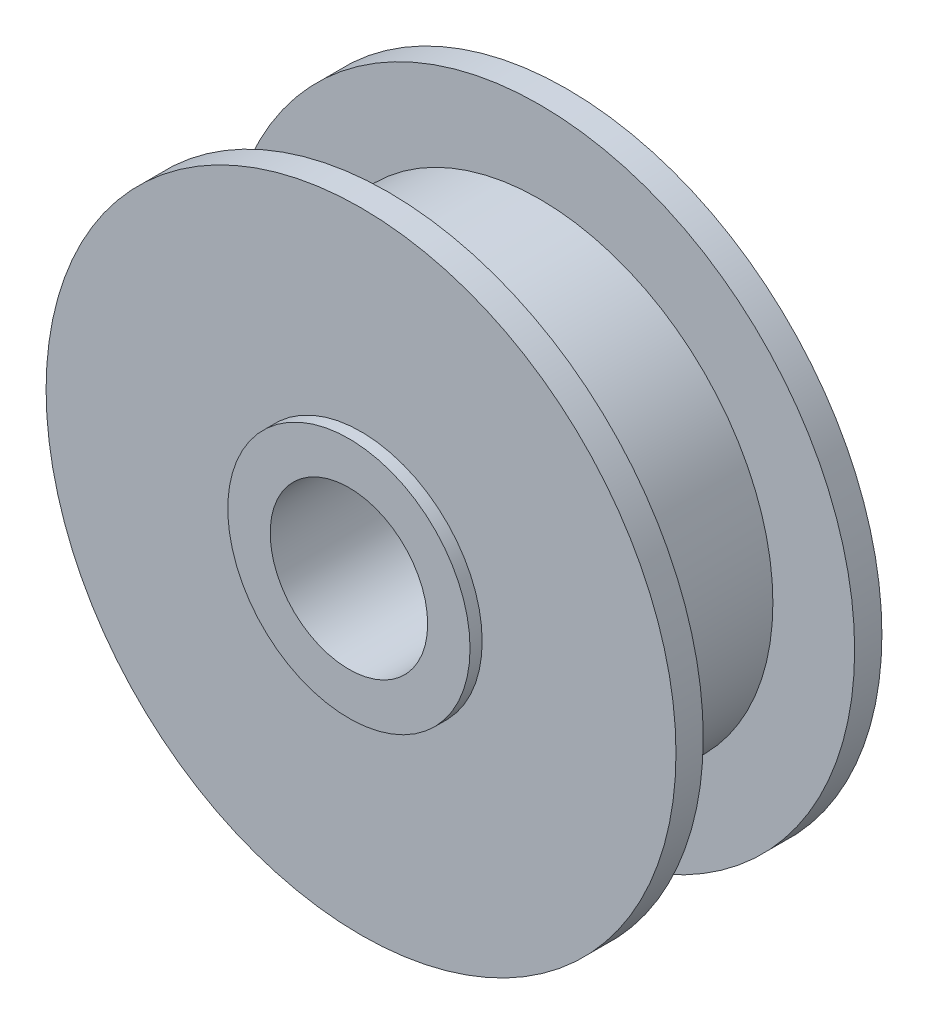
SolidWorks part; units mm, degrees
ref_plane "Front Plane" through (0, 0, 0) normal (0, 0, 1) x (1, 0, 0)
ref_plane "Top Plane" through (0, 0, 0) normal (0, 1, 0) x (1, 0, 0)
ref_plane "Right Plane" through (0, 0, 0) normal (1, 0, 0) x (0, 0, -1)
sketch "Sketch1" plane through (0, 0, 0) normal (1, 0, 0) x (0, 0, -1)
  line L0 (0, 1.3) -> (0, 2)
  line L1 (0, 2) -> (0.2, 2)
  line L2 (0.2, 2) -> (0.2, 5.2)
  line L3 (0.2, 5.2) -> (0.65, 5.2)
  line L4 (0.65, 5.2) -> (0.65, 3.85)
  line L5 (0.65, 3.85) -> (3.15, 3.85)
  line L6 (3.15, 3.85) -> (3.15, 5.2)
  line L7 (3.15, 5.2) -> (3.6, 5.2)
  line L8 (3.6, 5.2) -> (3.6, 2)
  line L9 (3.6, 2) -> (3.8, 2)
  line L10 (3.8, 2) -> (3.8, 1.3)
  line L11 (3.8, 1.3) -> (0, 1.3)
  line L12 (0, 0) -> (3.8, 0) construction
  dimension "D1" = 5.2
  dimension "D2" = 2
  dimension "D3" = 2.5
  dimension "D4" = 1.3
  dimension "D5" = 3.85
  dimension "D6" = 0.45
  dimension "D7" = 0.2
revolve "Revolve1" add sketch "Sketch1" angle 360 about L12
